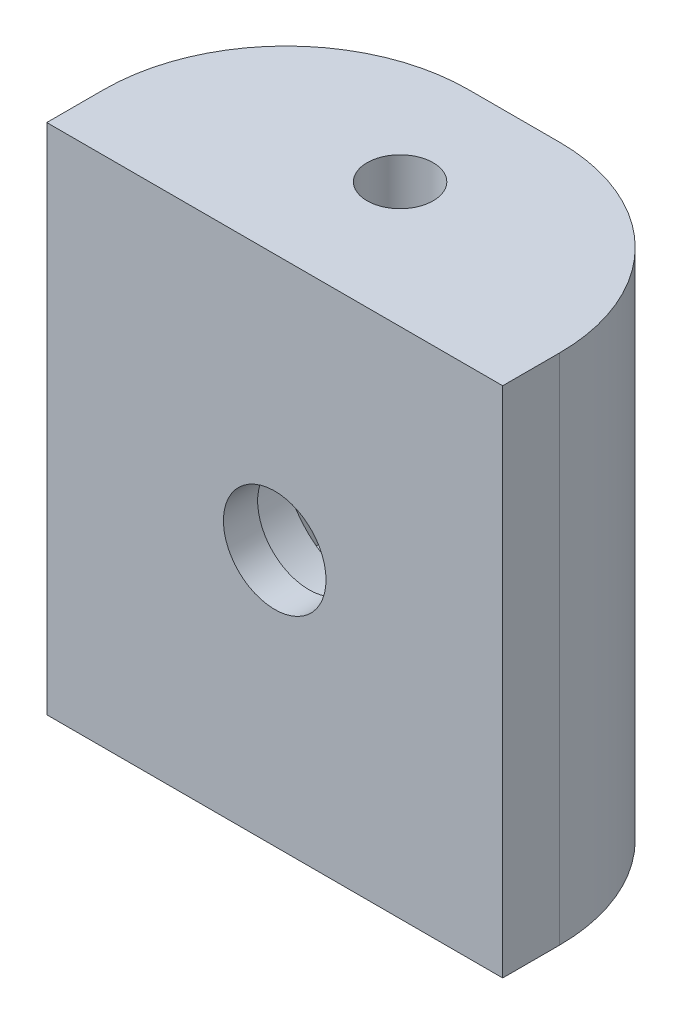
SolidWorks part; units mm, degrees
ref_plane "Front" through (0, 0, 0) normal (0, 0, 1) x (1, 0, 0)
ref_plane "Top" through (0, 0, 0) normal (0, 1, 0) x (1, 0, 0)
ref_plane "Right" through (0, 0, 0) normal (1, 0, 0) x (0, 0, -1)
sketch "Sketch1" plane through (0, 0, 0) normal (0, 0, 1) x (1, 0, 0)
  line L1 (0, 0) -> (20, 0)
  line L2 (0, 0) -> (0, -22.5)
  line L3 (0, -22.5) -> (20, -22.5)
  line L4 (20, 0) -> (20, -22.5)
  dimension "D1" = 20
  dimension "D2" = 22.5
extrude "Boss-Extrude1" add sketch "Sketch1" along normal blind 4
sketch "Sketch2" plane through (0, 0, 4) normal (0, 0, 1) x (1, 0, 0)
  line L0 (0, -22.5) -> (20, -22.5) construction
  circle A0 centre (10, -11.25) radius 2.25
  dimension "D1" = 4.5
  dimension "D2" = 11.25
extrude "Cut-Extrude1" cut sketch "Sketch2" against normal blind 1.5
sketch "Sketch3" plane through (0, 0, 2.5) normal (0, 0, 1) x (1, 0, 0)
  circle A0 centre (10, -11.25) radius 3.65
  dimension "D1" = 7.3
extrude "Cut-Extrude2" cut sketch "Sketch3" against normal blind 2.5
sketch "Sketch4" plane through (0, 0, 0) normal (0, 0, -1) x (-1, 0, 0)
  line L0 (0, 0) -> (0, -22.5) construction
  line L1 (-20, 0) -> (0, 0)
  line L2 (-20, 0) -> (-20, -4.5)
  line L3 (-20, -4.5) -> (0, -4.5)
  line L4 (0, 0) -> (0, -4.5)
  line L5 (-20, -22.5) -> (-20, 0) construction
  line L6 (0, -22.5) -> (-20, -22.5)
  line L7 (0, -22.5) -> (0, -18)
  line L8 (0, -18) -> (-20, -18)
  line L9 (-20, -22.5) -> (-20, -18)
  line L11 (-20, -4.5) -> (-16, -4.5)
  line L12 (-20, -4.5) -> (-20, -18)
  line L13 (-20, -18) -> (-16, -18)
  line L14 (-16, -4.5) -> (-16, -18)
  line L15 (0, -4.5) -> (-4, -4.5)
  line L16 (0, -4.5) -> (0, -18)
  line L17 (0, -18) -> (-4, -18)
  line L18 (-4, -4.5) -> (-4, -18)
  line M20 (0, -22.5) -> (0, 0)
  line M21 (0, 0) -> (-20, 0)
  line M22 (-20, 0) -> (-20, -22.5)
  line M23 (-20, -22.5) -> (0, -22.5)
  dimension "D1" = 4.5
  dimension "D2" = 4.5
  dimension "D3" = 4
  dimension "D4" = 4
extrude "Boss-Extrude2" add sketch "Sketch4" along normal blind 6.5 contours L14 L3 L8 M22 | L3 M22 M20 M21 | L3 L18 L8 M20 | L8 M20 M22 M23 region at (10, -2.25, 0) region at (18, -11.25, 0) region at (2, -11.25, 0) region at (10, -20.25, 0)
sketch "Sketch5" plane through (0, 0, 0) normal (0, 1, 0) x (1, 0, 0)
  line L0 (20, -4) -> (0, -4) construction
  circle A0 centre (10, 1.5) radius 1.45
  dimension "D1" = 2.9
  dimension "D2" = 5.5
extrude "Cut-Extrude3" cut sketch "Sketch5" against normal through all
fillet "Fillet1" radius 8 2 edges at (0, -11.25, -6.5) (20, -11.25, -6.5)
